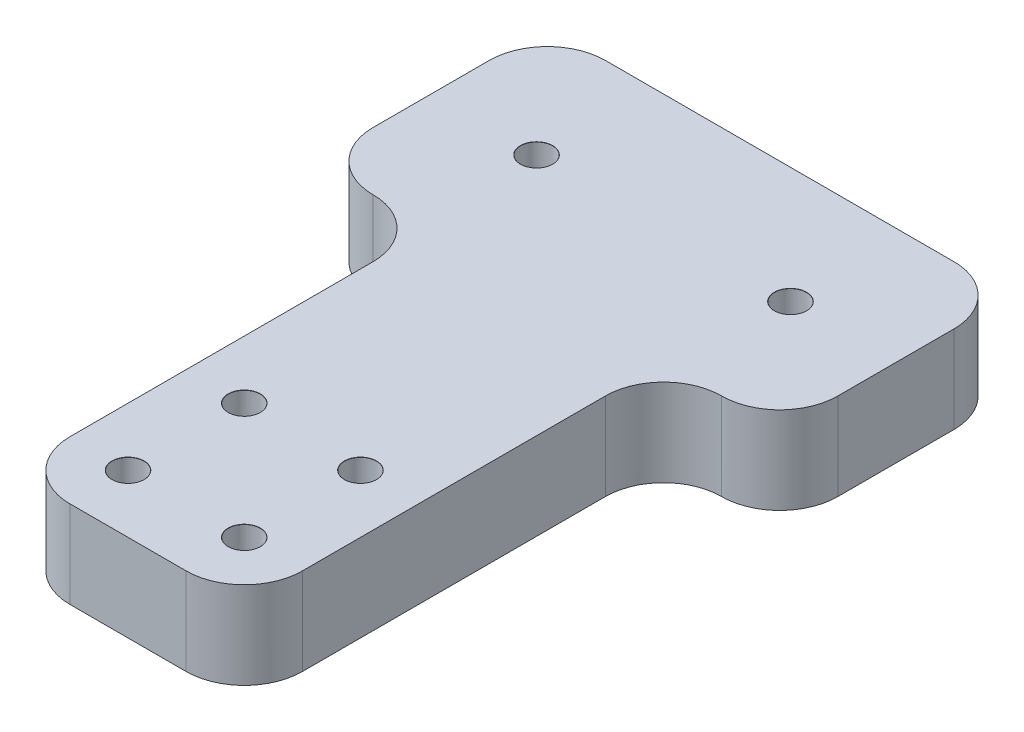
SolidWorks part; units mm, degrees
ref_plane "Front Plane" through (0, 0, 0) normal (0, 0, 1) x (1, 0, 0)
ref_plane "Top Plane" through (0, 0, 0) normal (0, 1, 0) x (1, 0, 0)
ref_plane "Right Plane" through (0, 0, 0) normal (1, 0, 0) x (0, 0, -1)
sketch "Sketch1" plane through (0, 0, 0) normal (0, 1, 0) x (1, 0, 0)
  line L1 (0, 0) -> (40, 0)
  line L7 (40, 0) -> (40, 72.15)
  line L8 (0, 0) -> (0, 72.15)
  line L13 (0, 72.15) -> (-20, 72.15)
  line L14 (-20, 72.15) -> (-20, 112.15)
  line L15 (-20, 112.15) -> (60, 112.15)
  line L16 (60, 112.15) -> (60, 72.15)
  line L17 (60, 72.15) -> (40, 72.15)
  line L18 (-1.85, 92.15) -> (41.85, 92.15) construction
  line L20 (10, 30) -> (30, 30) construction
  line L21 (10, 30) -> (10, 10) construction
  line L22 (10, 10) -> (30, 10) construction
  line L23 (30, 30) -> (30, 10) construction
  point P1 (41.85, 92.15)
  point P12 (-1.85, 92.15)
  point P13 (-20, 92.15)
  point P15 (20, 0)
  point P16 (20, 112.15)
  point P17 (20, 92.15)
  point P21 (10, 30)
  point P22 (30, 30)
  point P23 (10, 10)
  point P24 (30, 10)
  point P25 (20, 10)
  dimension "D1" = 40
  dimension "D2" = 92.15
  dimension "D3" = 40
  dimension "D4" = 43.7
  dimension "D5" = 20
  dimension "D6" = 20
  dimension "D7" = 10
extrude "Boss-Extrude1" add sketch "Sketch1" along normal blind 15 contours L1 region at (20, 0, -65.5591)
sketch "Sketch6" plane through (0, 15, 0) normal (0, 1, 0) x (1, 0, 0)
  point P0 (-1.85, 92.15)
  point P3 (41.85, 92.15)
  point P6 (10, 30)
  point P9 (30, 30)
  point P12 (10, 10)
  point P15 (30, 10)
hole_wizard "M5 Clearance Hole1" positions "Sketch6" profile "Sketch5" hole size "M5" standard "ANSI Metric" end condition through all
sketch "Sketch5" plane through (-1.85, 15, -92.15) normal (1, 0, 0) x (0, 0, 1)
  line L0 (0, 0) -> (0, 15)
  line L1 (0, 15) -> (2.75, 15)
  line L2 (2.75, 15) -> (2.75, 0.025)
  line L3 (2.75, 0.025) -> (2.775, 0)
  line L5 (2.775, 0) -> (0, 0)
  line L6 (-2.75, 0.025) -> (-2.775, 0) construction
  line L11 (0, -6.35) -> (0, 107.95) construction
  dimension "Thru Hole Dia." = 5.5
  dimension "Thru Hole Depth" = 15
  dimension "Near C'Sink Dia." = 5.55
  dimension "Near C'Sink Angle" = 90
fillet "Fillet1" radius 10 8 edges at (0, 7.5, 0) (40, 7.5, 0) (40, 7.5, -72.15) (60, 7.5, -72.15) (60, 7.5, -112.15) (-20, 7.5, -112.15) (-20, 7.5, -72.15) (0, 7.5, -72.15) first distance on face at (20, 7.5, 0) first distance on face at (50, 7.5, -72.15) first distance on face at (20, 7.5, -112.15) first distance on face at (-10, 7.5, -72.15)
